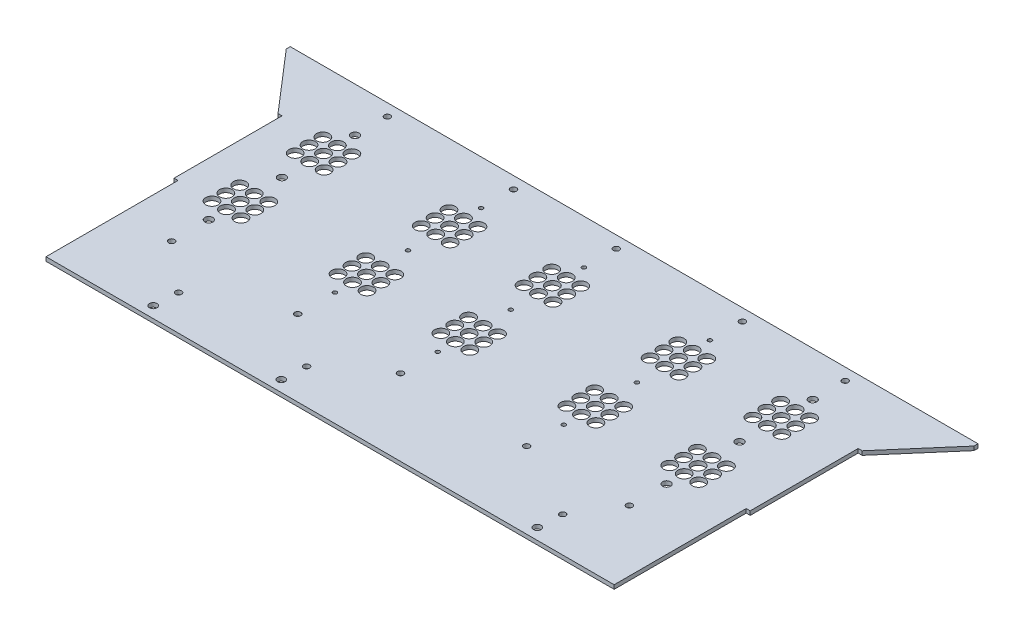
SolidWorks part; units mm, degrees
material "6061-T6 (SS)"
ref_plane "X-Y Datum" through (0, 0, 0) normal (0, 0, 1) x (1, 0, 0)
ref_plane "X-Z Datum" through (0, 0, 0) normal (0, 1, 0) x (1, 0, 0)
ref_plane "Y-Z Datum" through (0, 0, 0) normal (1, 0, 0) x (0, 0, -1)
sketch "Sketch1" plane through (0, 0, 0) normal (0, 0, 1) x (1, 0, 0)
  line L1 (-228.6114, -1.5875) -> (228.6114, -1.5875)
  line L2 (-228.6114, -1.5875) -> (-228.6114, 1.5875)
  line L3 (-228.6114, 1.5875) -> (228.6114, 1.5875)
  line L4 (228.6114, -1.5875) -> (228.6114, 1.5875)
  line L5 (-228.6114, -1.5875) -> (228.6114, 1.5875) construction
  line L6 (-228.6114, 1.5875) -> (228.6114, -1.5875) construction
  point P0 (0, 0)
  dimension "D1" = 3.175
  dimension "D2" = 457.2229
extrude "Boss-Extrude1" add sketch "Sketch1" along normal blind 241.2744
sketch "Sketch4" plane through (0, -1.5875, 0) normal (0, -1, 0) x (1, 0, 0)
  line L0 (-228.6114, 0) -> (-272.8862, 0)
  line L2 (-228.6114, 241.2744) -> (-228.6114, 0) construction
  line L3 (-228.6114, 50.8) -> (-228.6114, 0)
  line L4 (-272.8862, 0) -> (-272.8862, 3.175)
  line L6 (-228.6114, 50.8) -> (-231.7864, 50.8)
  line L7 (-231.7864, 50.8) -> (-272.8862, 3.175)
  line L31 (-228.6114, 0) -> (228.6114, 0)
  line L40 (-228.6114, 241.2744) -> (-228.6114, 0)
  line L41 (228.6114, 241.2744) -> (-228.6114, 241.2744)
  line L42 (228.6114, 0) -> (228.6114, 241.2744)
  line L51 (-228.6114, 0) -> (228.6114, 0)
  line L60 (-228.6114, 241.2744) -> (-228.6114, 0)
  line L61 (228.6114, 241.2744) -> (-228.6114, 241.2744)
  line L62 (228.6114, 0) -> (228.6114, 241.2744)
  line M15 (-228.6114, 241.2744) -> (-228.6114, 0)
  dimension "D1" = 44.2747
  dimension "D2" = 50.8
  dimension "D3" = 3.175
  dimension "D4" = 3.175
  dimension "D5" = 0
extrude "Boss-Extrude3" add sketch "Sketch4" against normal blind 3.175 contours L6 L7 L4 L0 M15 region at (-244.2491, -1.5875, 18.0626)
mirror "Mirror1" about plane through (0, 0, 0) normal (1, 0, 0) of "Boss-Extrude3"
sketch "Sketch5" plane through (0, -1.5875, 0) normal (0, -1, 0) x (1, 0, 0)
  line L1 (-228.6114, 241.2744) -> (-225.4364, 241.2744)
  line L2 (-228.6114, 241.2744) -> (-228.6114, 136.4994)
  line L3 (-228.6114, 136.4994) -> (-225.4364, 136.4994)
  line L4 (-225.4364, 241.2744) -> (-225.4364, 136.4994)
  dimension "D1" = 3.175
  dimension "D2" = 104.775
extrude "Cut-Extrude2" cut sketch "Sketch5" against normal blind 3.175
mirror "Mirror2" about plane through (0, 0, 0) normal (1, 0, 0) of "Cut-Extrude2"
sketch "Sketch37" plane through (0, 1.5875, 0) normal (0, 1, 0) x (1, 0, 0)
  line L0 (-149.2364, -241.2744) -> (-149.2364, -232.3844) construction
  line L1 (225.4364, -241.2744) -> (-225.4364, -241.2744) construction
  line L2 (-225.4364, -136.4994) -> (-225.4364, -241.2744) construction
  circle A0 centre (-149.2364, -232.3844) radius 3
  dimension "D1" = 8.89
  dimension "D3" = 6
  dimension "D2" = 76.2
extrude "Cut-Extrude12" cut sketch "Sketch37" against normal blind 3.175
pattern_linear "LPattern31" count 4 spacing 101.6 along (1, 0, 0) skipping (2, 0) of "Cut-Extrude12"
sketch "Sketch38" plane through (0, 1.5875, 0) normal (0, 1, 0) x (1, 0, 0)
  point P0 (-186.2355, -180.775)
  point P1 (-186.2355, -9.525)
hole_wizard "M4 Clearance Hole1" positions "Sketch38" profile "Sketch39" hole size "M4" standard "ANSI Metric" end condition through all
sketch "Sketch39" plane through (-186.2355, 1.5875, 180.775) normal (1, 0, 0) x (0, 0, 1)
  line L0 (0, 0) -> (0, 3.175)
  line L1 (0, 3.175) -> (2.4, 3.175)
  line L2 (2.4, 3.175) -> (2.4, 0)
  line L5 (2.4, 0) -> (0, 0)
  line L11 (0, -6.35) -> (0, 107.95) construction
  dimension "Thru Hole Dia." = 4.8
  dimension "Thru Hole Depth" = 3.175
pattern_linear "LPattern32" count 3 spacing 181.614 along (1, 0, 0) of "M4 Clearance Hole1"
sketch "Sketch41" plane through (0, 1.5875, 0) normal (0, 1, 0) x (1, 0, 0)
  point P0 (-86.1905, -180.775)
  point P1 (-86.1905, -9.525)
hole_wizard "M4 Clearance Hole2" positions "Sketch41" profile "Sketch42" hole size "M4" standard "ANSI Metric" end condition through all
sketch "Sketch42" plane through (-86.1905, 1.5875, 180.775) normal (1, 0, 0) x (0, 0, 1)
  line L0 (0, 0) -> (0, 3.175)
  line L1 (0, 3.175) -> (2.4, 3.175)
  line L2 (2.4, 3.175) -> (2.4, 0)
  line L5 (2.4, 0) -> (0, 0)
  line L11 (0, -6.35) -> (0, 107.95) construction
  dimension "Thru Hole Dia." = 4.8
  dimension "Thru Hole Depth" = 3.175
pattern_linear "LPattern33" count 2 spacing 181.614 along (1, 0, 0) of "M4 Clearance Hole2"
sketch "Sketch43" plane through (0, 1.5875, 0) normal (0, 1, 0) x (1, 0, 0)
  point P0 (-148.21, -213.285)
  point P1 (-46.61, -213.285)
  point P3 (156.59, -213.285)
hole_wizard "M4 Clearance Hole3" positions "Sketch43" profile "Sketch44" hole size "M4" standard "ANSI Metric" end condition through all
sketch "Sketch44" plane through (-148.21, 1.5875, 213.285) normal (1, 0, 0) x (0, 0, 1)
  line L0 (0, 0) -> (0, 3.175)
  line L1 (0, 3.175) -> (2.4, 3.175)
  line L2 (2.4, 3.175) -> (2.4, 0)
  line L5 (2.4, 0) -> (0, 0)
  line L11 (0, -6.35) -> (0, 107.95) construction
  dimension "Thru Hole Dia." = 4.8
  dimension "Thru Hole Depth" = 3.175
sketch "Sketch45" plane through (0, 1.5875, 0) normal (0, 1, 0) x (1, 0, 0)
  circle A0 centre (-74.6905, -115.2567) radius 5 construction
  circle A1 centre (-86.1905, -115.2567) radius 5 construction
  circle A2 centre (-97.6905, -115.2567) radius 5 construction
  circle A3 centre (-97.6905, -126.2567) radius 5 construction
  circle A4 centre (-86.1905, -126.2567) radius 5 construction
  circle A5 centre (-74.6905, -126.2567) radius 5 construction
  circle A6 centre (-97.6905, -137.2567) radius 5 construction
  circle A7 centre (-74.6905, -137.2567) radius 5 construction
  circle A8 centre (-86.1905, -137.2567) radius 5 construction
  circle A9 centre (-74.6905, -115.2567) radius 5
  circle A10 centre (-86.1905, -115.2567) radius 5
  circle A11 centre (-97.6905, -115.2567) radius 5
  circle A12 centre (-97.6905, -126.2567) radius 5
  circle A13 centre (-86.1905, -126.2567) radius 5
  circle A14 centre (-74.6905, -126.2567) radius 5
  circle A15 centre (-97.6905, -137.2567) radius 5
  circle A16 centre (-74.6905, -137.2567) radius 5
  circle A17 centre (-86.1905, -137.2567) radius 5
  circle A18 centre (-97.6905, -71.2567) radius 5 construction
  circle A19 centre (-86.1905, -71.2567) radius 5 construction
  circle A20 centre (-74.6905, -71.2567) radius 5 construction
  circle A21 centre (-74.6905, -60.2567) radius 5 construction
  circle A22 centre (-86.1905, -60.2567) radius 5 construction
  circle A23 centre (-97.6905, -60.2567) radius 5 construction
  circle A24 centre (-97.6905, -49.2567) radius 5 construction
  circle A25 centre (-86.1905, -49.2567) radius 5 construction
  circle A26 centre (-74.6905, -49.2567) radius 5 construction
  circle A27 centre (-97.6905, -71.2567) radius 5
  circle A28 centre (-86.1905, -71.2567) radius 5
  circle A29 centre (-74.6905, -71.2567) radius 5
  circle A30 centre (-74.6905, -60.2567) radius 5
  circle A31 centre (-86.1905, -60.2567) radius 5
  circle A32 centre (-97.6905, -60.2567) radius 5
  circle A33 centre (-97.6905, -49.2567) radius 5
  circle A34 centre (-86.1905, -49.2567) radius 5
  circle A35 centre (-74.6905, -49.2567) radius 5
extrude "Cut-Extrude13" cut sketch "Sketch45" against normal through all
pattern_linear "LPattern34" count 2 spacing 181.614 along (1, 0, 0) of "Cut-Extrude13"
sketch "Sketch46" plane through (0, 1.5875, 0) normal (0, 1, 0) x (1, 0, 0)
  circle A0 centre (-174.7355, -71.2567) radius 5 construction
  circle A1 centre (-186.2355, -71.2567) radius 5 construction
  circle A2 centre (-197.7355, -71.2567) radius 5 construction
  circle A3 centre (-197.7355, -60.2567) radius 5 construction
  circle A4 centre (-186.2355, -60.2567) radius 5 construction
  circle A5 centre (-174.7355, -60.2567) radius 5 construction
  circle A6 centre (-174.7355, -49.2567) radius 5 construction
  circle A7 centre (-186.2355, -49.2567) radius 5 construction
  circle A8 centre (-197.7355, -49.2567) radius 5 construction
  circle A9 centre (-174.7355, -71.2567) radius 5
  circle A10 centre (-186.2355, -71.2567) radius 5
  circle A11 centre (-197.7355, -71.2567) radius 5
  circle A12 centre (-197.7355, -60.2567) radius 5
  circle A13 centre (-186.2355, -60.2567) radius 5
  circle A14 centre (-174.7355, -60.2567) radius 5
  circle A15 centre (-174.7355, -49.2567) radius 5
  circle A16 centre (-186.2355, -49.2567) radius 5
  circle A17 centre (-197.7355, -49.2567) radius 5
  circle A18 centre (-174.7355, -137.2567) radius 5 construction
  circle A19 centre (-186.2355, -137.2567) radius 5 construction
  circle A20 centre (-197.7355, -137.2567) radius 5 construction
  circle A21 centre (-197.7355, -126.2567) radius 5 construction
  circle A22 centre (-186.2355, -126.2567) radius 5 construction
  circle A23 centre (-174.7355, -126.2567) radius 5 construction
  circle A24 centre (-197.7355, -115.2567) radius 5 construction
  circle A25 centre (-186.2355, -115.2567) radius 5 construction
  circle A26 centre (-174.7355, -115.2567) radius 5 construction
  circle A27 centre (-174.7355, -137.2567) radius 5
  circle A28 centre (-186.2355, -137.2567) radius 5
  circle A29 centre (-197.7355, -137.2567) radius 5
  circle A30 centre (-197.7355, -126.2567) radius 5
  circle A31 centre (-186.2355, -126.2567) radius 5
  circle A32 centre (-174.7355, -126.2567) radius 5
  circle A33 centre (-197.7355, -115.2567) radius 5
  circle A34 centre (-186.2355, -115.2567) radius 5
  circle A35 centre (-174.7355, -115.2567) radius 5
extrude "Cut-Extrude14" cut sketch "Sketch46" against normal through all
pattern_linear "LPattern35" count 3 spacing 181.614 along (1, 0, 0) of "Cut-Extrude14"
sketch "Sketch47" plane through (0, 1.5875, 0) normal (0, 1, 0) x (1, 0, 0)
  circle A0 centre (176.9925, -151.2567) radius 3.175
  circle A1 centre (176.9642, -93.2567) radius 3.175
  circle A2 centre (176.9925, -35.2567) radius 3.175
  circle A3 centre (-186.2355, -35.2567) radius 3.175
  circle A4 centre (-186.2355, -93.2567) radius 3.175
  circle A5 centre (-186.2355, -151.2567) radius 3.175
  point P0 (-186.2355, -151.2567)
  point P1 (-186.2355, -93.2567)
  point P3 (-186.2355, -35.2567)
  point P5 (176.9642, -93.2567)
  point P7 (176.9925, -35.2567)
  point P9 (176.9925, -151.2567)
  dimension "D1" = 6.35
sketch "Sketch48" plane through (0, 1.5875, 0) normal (0, 1, 0) x (1, 0, 0)
  circle A0 centre (95.4235, -151.2567) radius 1.5875
  circle A1 centre (95.4235, -93.2567) radius 1.5875
  circle A2 centre (95.4235, -35.2567) radius 1.5875
  circle A3 centre (-4.6215, -35.2567) radius 1.5875
  circle A4 centre (-4.6215, -93.2567) radius 1.5875
  circle A5 centre (-4.6215, -151.2567) radius 1.5875
  circle A6 centre (-86.1905, -35.2567) radius 1.5875
  circle A7 centre (-86.1905, -93.2567) radius 1.5875
  circle A8 centre (-86.1905, -151.2567) radius 1.5875
  point P0 (-86.1905, -35.2567)
  point P1 (-86.1905, -93.2567)
  point P2 (-86.1905, -151.2567)
  point P5 (-4.6215, -151.2567)
  point P7 (-4.6215, -93.2567)
  point P9 (-4.6215, -35.2567)
  point P11 (95.4235, -35.2567)
  point P13 (95.4235, -93.2567)
  point P15 (95.4235, -151.2567)
  dimension "D1" = 3.175
extrude "Cut-Extrude15" cut sketch "Sketch47" against normal through all
extrude "Cut-Extrude16" cut sketch "Sketch48" against normal through all
